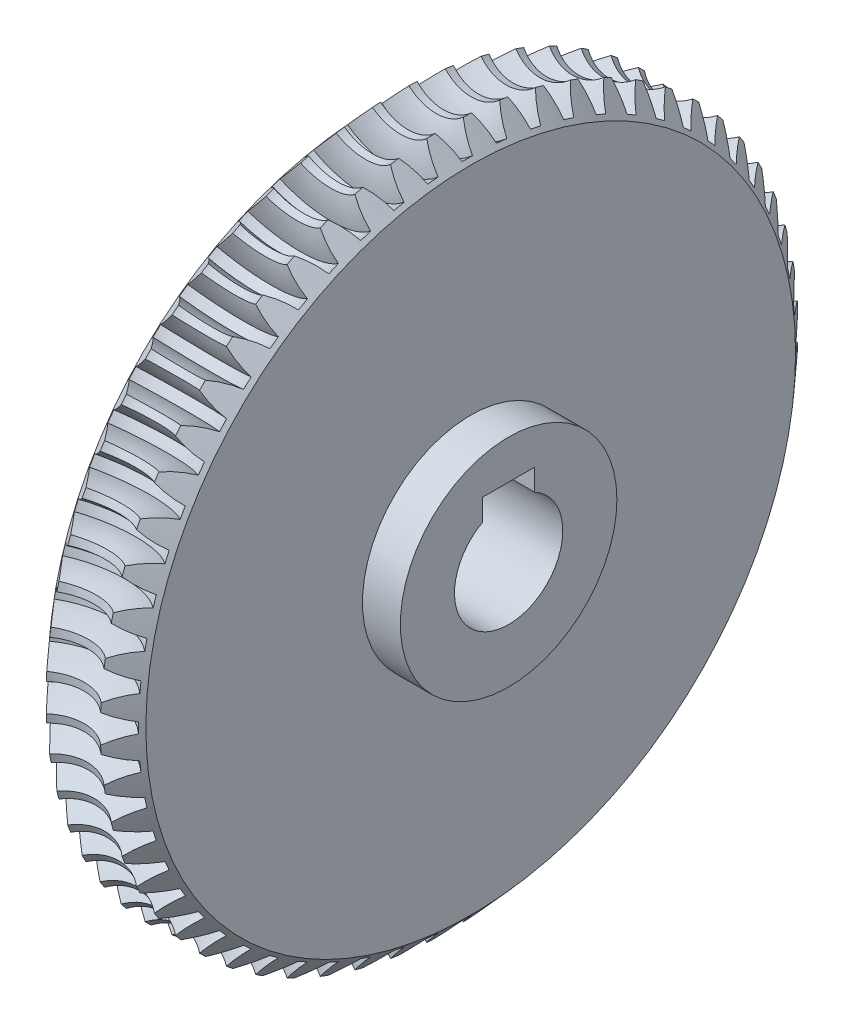
SolidWorks part; units mm, degrees
ref_plane "Alzado" through (0, 0, 0) normal (0, 0, 1) x (1, 0, 0)
ref_plane "Planta" through (0, 0, 0) normal (0, 1, 0) x (1, 0, 0)
ref_plane "Vista lateral" through (0, 0, 0) normal (1, 0, 0) x (0, 0, -1)
sketch "Croquis1" plane through (0, 0, 0) normal (0, 0, 1) x (1, 0, 0)
  line L0 (-3.1358, 40.2658) -> (-5.625, 37.5)
  line L1 (-5.625, 6.25) -> (5.625, 6.25)
  line L2 (-5.625, 6.25) -> (-5.625, 37.5)
  line L4 (5.625, 6.25) -> (5.625, 37.5)
  line L5 (3.1358, 40.2658) -> (5.625, 37.5)
  line L6 (0, 0) -> (-20.152, 0) construction
  arc A2 (-3.1358, 40.2658) -> (3.1358, 40.2658) centre (0, 43.75) ccw
  point P4 (0, 6.25)
  dimension "D4" = 4.6875
  dimension "D1" = 31.25
  dimension "D2" = 11.25
  dimension "D3" = 6.25
revolve "Revolución1" add sketch "Croquis1" angle 360 about L6
sketch "Croquis2" plane through (0, 0, 0) normal (1, 0, 0) x (0, 0, -1)
  line L0 (0, 43.75) -> (27.3643, 43.75) construction
  line L1 (0, 0) -> (0, 40.2658) construction
  line L2 (0, 40.2658) -> (0, 37.5) construction
  line L3 (0, 0) -> (1.054, 40.252) construction
  line L5 (-3.3071, 41.4411) -> (3.3071, 41.4411)
  arc A0 (0.9816, 37.4871) -> (-0.9816, 37.4871) centre (0, 0) ccw construction
  arc A1 (0.5994, 35.9325) -> (-0.5994, 35.9325) centre (0, 0) ccw
  circle A3 centre (0, 0) radius 38.75 construction
  arc A5 (1.4719, 38.722) -> (-1.4719, 38.722) centre (0, 0) ccw construction
  circle A6 centre (0, 0) radius 40.2658 construction
  arc A7 (3.3071, 41.4411) -> (0.5994, 35.9325) centre (11.1636, 34.1596) ccw
  arc A8 (-3.3071, 41.4411) -> (-0.5994, 35.9325) centre (-11.1636, 34.1596) cw
  circle A9 centre (0, 0) radius 37.5 construction
  point P24 (0, 41.4411)
  dimension "D1" = 75
  dimension "D4" = 1.5
  dimension "D3" = 1.25
revolve "Cortar-Revolución2" cut sketch "Croquis2" angle 360 about L0
pattern_circular "MatrizC1" count 60 every 6 about axis through (0, 0, 0) along (-1, 0, 0) of "Cortar-Revolución2"
sketch "Croquis3" plane through (0, 0, 0) normal (1, 0, 0) x (0, 0, -1)
  line L5 (-3, 5.4829) -> (3, 5.4829)
  line L6 (-3, 5.4829) -> (-3, 7.9829)
  line L7 (-3, 7.9829) -> (3, 7.9829)
  line L8 (3, 5.4829) -> (3, 7.9829)
  circle A1 centre (0, 0) radius 12.5
  circle A2 centre (0, 0) radius 6.25 construction
  circle A3 centre (0, 0) radius 6.25
  dimension "D1" = 25
  dimension "D2" = 2.5
  dimension "D3" = 6
extrude "Saliente-Extruir1" add sketch "Croquis3" along normal mid plane 20 contours A1 L8 L6 L7 region at (0, 0, 12.1464)
sketch "Croquis4" plane through (0, 0, 0) normal (1, 0, 0) x (0, 0, -1)
  circle A0 centre (0, 0) radius 38.75
  dimension "D1" = 77.5
